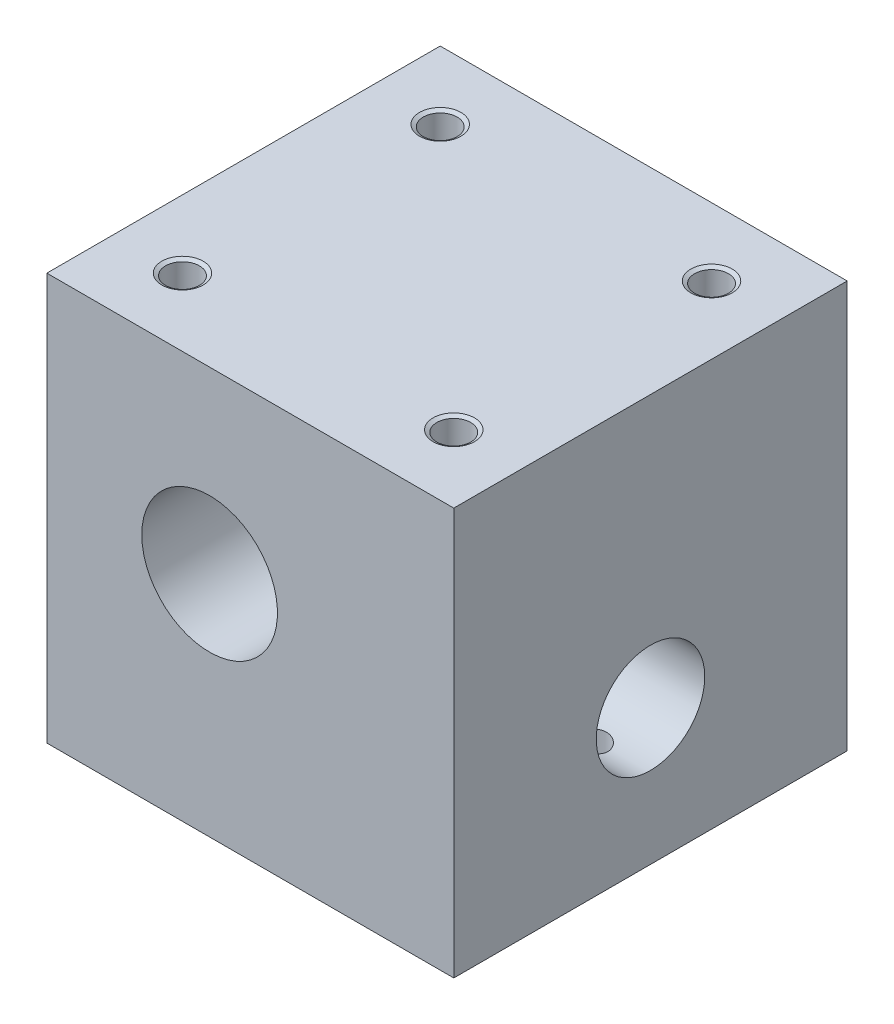
SolidWorks part; units mm, degrees
material "6063-T5"
ref_plane "Piano frontale" through (0, 0, 0) normal (0, 0, 1) x (1, 0, 0)
ref_plane "Piano superiore" through (0, 0, 0) normal (0, 1, 0) x (1, 0, 0)
ref_plane "Piano destro" through (0, 0, 0) normal (1, 0, 0) x (0, 0, -1)
sketch "Schizzo1" plane through (0, 0, 0) normal (0, 0, 1) x (1, 0, 0)
  line L0 (12, 6.5764) -> (12, 28.444) construction
  line L1 (0, 0) -> (30, 0)
  line L2 (0, 0) -> (0, 30)
  line L3 (0, 30) -> (30, 30)
  line L4 (30, 0) -> (30, 30)
  line L5 (6.315, 16.8) -> (24.6155, 16.8) construction
  circle A0 centre (12, 16.8) radius 5
  dimension "D3" = 10
  dimension "D1" = 30
  dimension "D2" = 30
  dimension "D4" = 12
  dimension "D5" = 13.2
extrude "Estrusione-Estrusione1" add sketch "Schizzo1" along normal blind 29
sketch "Schizzo3" plane through (30, 0, 0) normal (1, 0, 0) x (0, 0, -1)
  line L2 (-14.5, 10.16) -> (-14.5, 24.3684) construction
  line L3 (-29, 0) -> (-29, 30) construction
  line L4 (0, 0) -> (0, 30) construction
  line L5 (-29, 0) -> (0, 0) construction
  point P0 (-14.5, 10)
  dimension "D1" = 10
hole_wizard "Foro Ø8.0 (8)-1" positions "Schizzo5" profile "Schizzo4" hole size "Ø8.0" standard "ISO"
sketch "Schizzo5" plane through (30, 0, 0) normal (1, 0, 0) x (0, 0, -1)
  point P0 (-14.5, 10)
sketch "Schizzo4" plane through (30, 10, 14.5) normal (0, 1, 0) x (0, 0, -1)
  line L0 (0, 0) -> (0, 14.4034)
  line L1 (0, 14.4034) -> (4, 12)
  line L2 (4, 12) -> (4, 0)
  line L5 (4, 0) -> (0, 0)
  line L10 (0, 14.4034) -> (-4, 12) construction
  line L11 (0, -6.35) -> (0, 107.95) construction
  dimension "Hole Dia." = 8
  dimension "Hole Depth" = 12
  dimension "Drill Angle" = 118
sketch "Schizzo6" plane through (0, 30, 0) normal (0, 1, 0) x (1, 0, 0)
  line L0 (-7.6843, -24) -> (41.504, -24) construction
  line L1 (0, -29) -> (0, 0) construction
  line L2 (30, -29) -> (0, -29) construction
  point P0 (5, -24)
  point P1 (25, -24)
  dimension "D1" = 20
  dimension "D2" = 5
  dimension "D3" = 5
hole_wizard "Foro filettato M3-1" positions "Schizzo8" profile "Schizzo7" tap size "M3" standard "ISO"
sketch "Schizzo8" plane through (0, 30, 0) normal (0, 1, 0) x (1, 0, 0)
  point P0 (5, -24)
  point P3 (25, -24)
sketch "Schizzo7" plane through (5, 30, 24) normal (1, 0, 0) x (0, 0, 1)
  line L0 (0, 0) -> (0, 9.2511)
  line L1 (0, 9.2511) -> (1.25, 8.5)
  line L2 (1.25, 8.5) -> (1.25, 0.1588)
  line L3 (1.25, 0.1588) -> (1.525, 0)
  line L5 (1.525, 0) -> (0, 0)
  line L6 (-1.25, 0.1588) -> (-1.525, 0) construction
  line L10 (0, 9.2511) -> (-1.25, 8.5) construction
  line L11 (0, -6.35) -> (0, 107.95) construction
  dimension "Tap Drill Dia." = 2.5
  dimension "Tap Drill Depth" = 8.5
  dimension "Near C'Sink Dia." = 3.05
  dimension "Near C'Sink Angle" = 120
  dimension "Drill Angle" = 118
cosmetic thread "Filettatura del foro1" parameters "D1"=6, "D2"=3
cosmetic thread "Filettatura del foro2" parameters "D1"=6, "D2"=3
ref_plane "Piano1" through (0, 0, 14.5) normal (0, 0, 1) x (1, 0, 0)
mirror "Specchia1" about plane through (0, 0, 14.5) normal (0, 0, 1) of "Foro filettato M3-1"
hole_wizard "Foro filettato M3-2" positions "Schizzo10" profile "Schizzo11" tap size "M3" standard "ISO"
sketch "Schizzo10" plane through (0, 0, 0) normal (0, -1, 0) x (-1, 0, 0)
  line L0 (0, 0) -> (-30, 0) construction
  line L1 (-30, -29) -> (-30, 0) construction
  point P0 (-26, -15)
  dimension "D1" = 15
  dimension "D2" = 4
sketch "Schizzo11" plane through (26, 0, 15) normal (1, 0, 0) x (0, 0, -1)
  line L0 (0, 0) -> (0, 9.2511)
  line L1 (0, 9.2511) -> (1.25, 8.5)
  line L2 (1.25, 8.5) -> (1.25, 0.1588)
  line L3 (1.25, 0.1588) -> (1.525, 0)
  line L5 (1.525, 0) -> (0, 0)
  line L6 (-1.25, 0.1588) -> (-1.525, 0) construction
  line L10 (0, 9.2511) -> (-1.25, 8.5) construction
  line L11 (0, -6.35) -> (0, 107.95) construction
  dimension "Tap Drill Dia." = 2.5
  dimension "Tap Drill Depth" = 8.5
  dimension "Near C'Sink Dia." = 3.05
  dimension "Near C'Sink Angle" = 120
  dimension "Drill Angle" = 118
